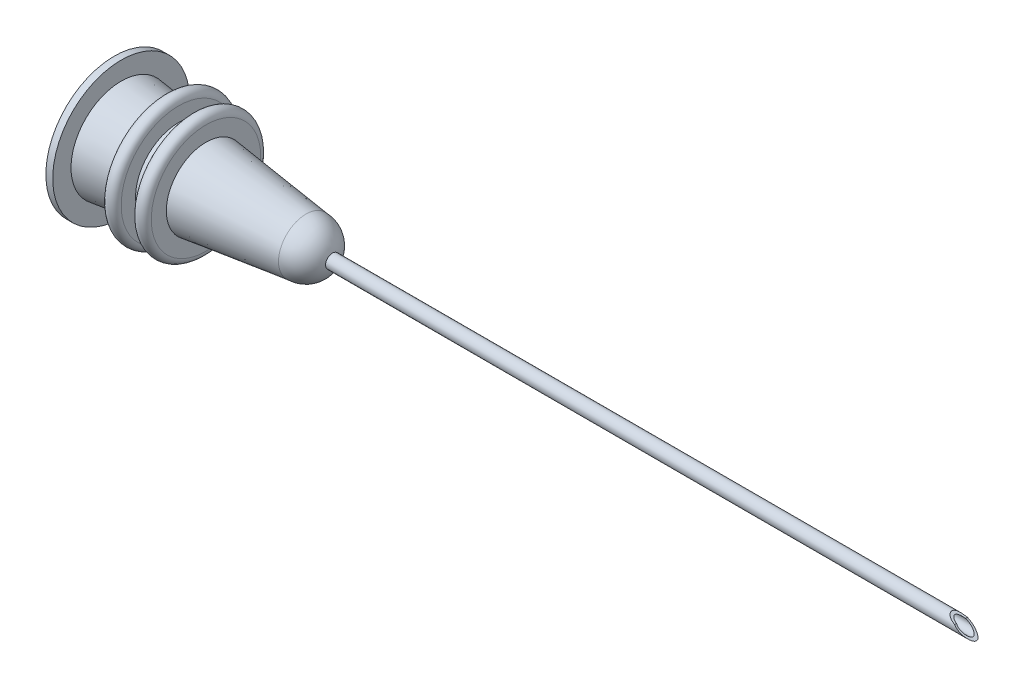
SolidWorks part; units mm, degrees
ref_plane "Front Plane" through (0, 0, 0) normal (0, 0, 1) x (1, 0, 0)
ref_plane "Top Plane" through (0, 0, 0) normal (0, 1, 0) x (1, 0, 0)
ref_plane "Right Plane" through (0, 0, 0) normal (1, 0, 0) x (0, 0, -1)
sketch "Sketch1" plane through (0, 0, 0) normal (0, 0, 1) x (1, 0, 0)
  line L0 (0, 0) -> (-10.5143, 0) construction
  line L1 (0, 0) -> (0, 2)
  line L2 (0, 2) -> (-7.3, 2.8996)
  line L3 (-13.5, 3.6636) -> (-13.5, 5)
  line L4 (-13.5, 5) -> (-14, 5)
  line L5 (-14, 5) -> (-14, 2.9695)
  line L6 (-14, 2.9695) -> (-1, 1.3676)
  line L7 (-1, 1.3676) -> (-1, 0)
  line L8 (-1, 0) -> (0, 0)
  line L9 (-9.3, 4.2) -> (-9.3, 3.146)
  line L10 (-10.3, 4.2) -> (-10.3, 3.2692)
  line L11 (-8.3, 4) -> (-8.3, 3.0228)
  line L12 (-7.3, 4) -> (-7.3, 2.8996)
  line L13 (-10.3, 3.2692) -> (-13.5, 3.6636)
  line L14 (-8.3, 3.0228) -> (-9.3, 3.146)
  arc A0 (-7.3, 4) -> (-8.3, 4) centre (-7.8, 4) ccw
  arc A1 (-9.3, 4.2) -> (-10.3, 4.2) centre (-9.8, 4.2) ccw
  dimension "D10" = 1
  dimension "D1" = 1
  dimension "D2" = 5
  dimension "D3" = 0.75
  dimension "D4" = 0.5
  dimension "D5" = 2
  dimension "D6" = 14
  dimension "D7" = 4
  dimension "D8" = 4.2
  dimension "D9" = 2
  dimension "D11" = 7.8
revolve "Revolve1" add sketch "Sketch1" angle 360 about L0
dome "Dome1" faces to dome 1 distance 2 reverse direction no elliptical dome no face at (0, 0, -2) parameters "D1"=2
sketch "Sketch2" plane through (-1, 0, 0) normal (-1, 0, 0) x (0, 0, 1)
  circle A0 centre (0, 0) radius 0.5
  dimension "D1" = 1
extrude "Cut-Extrude1" cut sketch "Sketch2" against normal blind 4
sketch "Sketch3" plane through (-1, 0, 0) normal (-1, 0, 0) x (0, 0, 1)
  circle A0 centre (0, 0) radius 0.5 construction
  circle A1 centre (0, 0) radius 0.5
extrude "Extrude-Thin1" add sketch "Sketch3" against normal blind 50 thin thin type one direction reverse wall 0.125
sketch "Sketch4" plane through (0, 0, 0) normal (0, 0, 1) x (1, 0, 0)
  line L0 (49, -0.5) -> (49, 7) construction
  line L1 (49, 0.5) -> (49, -0.5) construction
  line L2 (49, 0.5) -> (1.9365, 0.5) construction
  circle A0 centre (49, 3.5) radius 3.5
  point P4 (49, 0)
  dimension "D1" = 7
extrude "Cut-Extrude2" cut sketch "Sketch4" against normal mid plane 10
sketch "Sketch5" plane through (0, 0, 0) normal (0, 0, 1) x (1, 0, 0)
  line L0 (49, -0.5) -> (49, 8.2198) construction
  line L1 (49, -0.5) -> (51, -0.5) construction
  line L2 (51, -0.5) -> (51, 4.0826) construction
  circle A0 centre (51, 4.0826) radius 5
  dimension "D2" = 10
  dimension "D1" = 2
extrude "Cut-Extrude3" cut sketch "Sketch5" against normal mid plane 10
